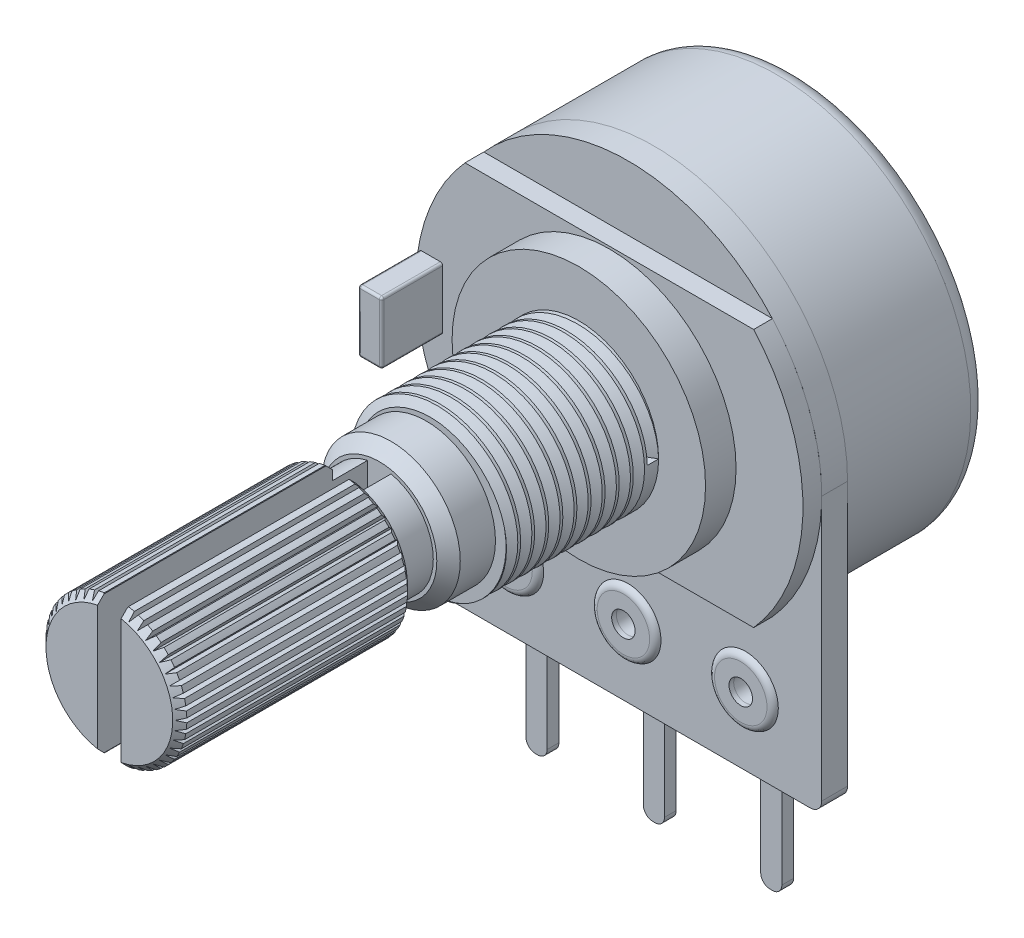
SolidWorks part; units mm, degrees
ref_plane "Ebene vorne" through (0, 0, 0) normal (0, 0, 1) x (1, 0, 0)
ref_plane "Ebene oben" through (0, 0, 0) normal (0, 1, 0) x (1, 0, 0)
ref_plane "Ebene rechts" through (0, 0, 0) normal (1, 0, 0) x (0, 0, -1)
sketch "Skizze1" plane through (0, 0, 0) normal (0, 0, 1) x (1, 0, 0)
  circle A0 centre (0, 0) radius 8.25
extrude "Aufsatz-Linear austragen1" add sketch "Skizze1" along normal blind 6
sketch "Skizze2" plane through (0, 0, 0) normal (0, 0, -1) x (-1, 0, 0)
  line L0 (8.25, 0) -> (6.85, 0)
  line L1 (6.85, 0) -> (6.85, -1.9)
  line L2 (6.85, -1.9) -> (8.0282, -1.9)
  circle A0 centre (0, 0) radius 8.25 construction
  arc A1 (8.25, 0) -> (8.0282, -1.9) centre (0, 0) cw
  dimension "D1" = 1.9
  dimension "D2" = 1.4
extrude "Schnitt-Linear austragen1" cut sketch "Skizze2" against normal blind 2.7
sketch "Skizze3" plane through (0, 0, 6) normal (0, 0, 1) x (1, 0, 0)
  line L0 (-8.25, 0) -> (-8.25, -11.75)
  line L1 (-8.25, -11.75) -> (8.25, -11.75)
  line L2 (8.25, -11.75) -> (8.25, 0)
  line L3 (0, 8.25) -> (19.4133, 8.25) construction
  line L4 (0, 0) -> (0, -11.75) construction
  arc A0 (8.25, 0) -> (-8.25, 0) centre (0, 0) ccw
  circle A1 centre (-5, -8.75) radius 0.5
  circle A2 centre (0, -8.75) radius 0.5
  circle A3 centre (5, -8.75) radius 0.5
  circle A4 centre (0, 0) radius 8.25 construction
  point P1 (0, 0)
  point P15 (0, 0)
  point P17 (0, 0)
  dimension "D2" = 1
  dimension "D1" = 20
  dimension "D3" = 3
  dimension "D4" = 10
extrude "Aufsatz-Linear austragen3" add sketch "Skizze3" along normal blind 1.1 separate body
sketch "Skizze4" plane through (0, 0, 6) normal (0, 0, -1) x (-1, 0, 0)
  line L0 (-6.8, -8.75) -> (-6.8, -12.75)
  line L1 (-6.8, -12.75) -> (-5.45, -12.75)
  line L2 (-5.45, -12.75) -> (-5.45, -16.3)
  line L3 (-5.05, -16.7) -> (-4.95, -16.7)
  line L4 (-4.55, -16.3) -> (-4.55, -12.75)
  line L5 (-4.55, -12.75) -> (-3.2, -12.75)
  line L6 (-3.2, -12.75) -> (-3.2, -8.75)
  line L7 (-5, -8.75) -> (-5, -16.7) construction
  line L8 (-5, -6.95) -> (-10.2754, -6.95) construction
  line L9 (-1.8, -8.75) -> (-1.8, -12.75)
  line L10 (-1.8, -12.75) -> (-0.45, -12.75)
  line L11 (-0.45, -12.75) -> (-0.45, -16.3)
  line L12 (-0.05, -16.7) -> (0.05, -16.7)
  line L13 (0.45, -16.3) -> (0.45, -12.75)
  line L14 (0.45, -12.75) -> (1.8, -12.75)
  line L15 (1.8, -12.75) -> (1.8, -8.75)
  line L16 (0, -8.75) -> (0, -16.7) construction
  line L17 (3.2, -8.75) -> (3.2, -12.75)
  line L18 (3.2, -12.75) -> (4.55, -12.75)
  line L19 (4.55, -12.75) -> (4.55, -16.3)
  line L20 (4.95, -16.7) -> (5.05, -16.7)
  line L21 (5.45, -16.3) -> (5.45, -12.75)
  line L22 (5.45, -12.75) -> (6.8, -12.75)
  line L23 (6.8, -12.75) -> (6.8, -8.75)
  line L24 (5, -8.75) -> (5, -16.7) construction
  arc A0 (-3.2, -8.75) -> (-6.8, -8.75) centre (-5, -8.75) ccw
  arc A1 (-4.95, -16.7) -> (-4.55, -16.3) centre (-4.95, -16.3) ccw
  arc A2 (-5.45, -16.3) -> (-5.05, -16.7) centre (-5.05, -16.3) ccw
  arc A3 (1.8, -8.75) -> (-1.8, -8.75) centre (0, -8.75) ccw
  arc A4 (0.05, -16.7) -> (0.45, -16.3) centre (0.05, -16.3) ccw
  arc A5 (-0.45, -16.3) -> (-0.05, -16.7) centre (-0.05, -16.3) ccw
  arc A6 (6.8, -8.75) -> (3.2, -8.75) centre (5, -8.75) ccw
  arc A7 (5.05, -16.7) -> (5.45, -16.3) centre (5.05, -16.3) ccw
  arc A8 (4.55, -16.3) -> (4.95, -16.7) centre (4.95, -16.3) ccw
  circle A9 centre (-5, -8.75) radius 0.5
  circle A10 centre (0, -8.75) radius 0.5
  circle A11 centre (5, -8.75) radius 0.5
  point P15 (-4.55, -16.7)
  point P18 (-5.45, -16.7)
  dimension "D1" = 0.9
  dimension "D5" = 0.4
  dimension "D2" = 3.6
  dimension "D3" = 5.8
  dimension "D4" = 9.75
  dimension "D6" = 3
extrude "Aufsatz-Linear austragen4" add sketch "Skizze4" along normal blind 0.5 separate body
sketch "Skizze5" plane through (0, 0, 7.1) normal (0, 0, 1) x (1, 0, 0)
  circle A0 centre (-5, -8.75) radius 1.4
  circle A1 centre (0, -8.75) radius 1.4
  circle A2 centre (5, -8.75) radius 1.4
  circle A3 centre (-5, -8.75) radius 0.5068
  circle A4 centre (0, -8.75) radius 0.5
  circle A5 centre (5, -8.75) radius 0.5
  dimension "D1" = 2.8
extrude "Aufsatz-Linear austragen5" add sketch "Skizze5" along normal blind 0.2 separate body
sketch "Skizze6" plane through (0, 0, 7.1) normal (0, 0, 1) x (1, 0, 0)
  line L0 (0, 0) -> (-5.8286, 0) construction
  line L1 (-6.1492, 5.5) -> (6.1492, 5.5)
  line L3 (-6.1492, -5.5) -> (6.1492, -5.5)
  arc A0 (6.1492, -5.5) -> (6.1492, 5.5) centre (0, 0) ccw
  arc A1 (-6.1492, 5.5) -> (-6.1492, -5.5) centre (0, 0) ccw
  dimension "D2" = 8.25
  dimension "D1" = 11
extrude "Aufsatz-Linear austragen6" add sketch "Skizze6" along normal blind 0.8 separate body
sketch "Skizze7" plane through (0, 0, 7.9) normal (0, 0, 1) x (1, 0, 0)
  line L1 (-8.1, 1.325) -> (-7.1, 1.325)
  line L2 (-8.1, 1.325) -> (-8.1, -1.325)
  line L3 (-8.1, -1.325) -> (-7.1, -1.325)
  line L4 (-7.1, 1.325) -> (-7.1, -1.325)
  line L5 (-8.1, 1.325) -> (-7.1, -1.325) construction
  line L6 (-8.1, -1.325) -> (-7.1, 1.325) construction
  circle A0 centre (0, 0) radius 5.4
  point P3 (-7.6, 0)
  point P8 (0, 0)
  dimension "D1" = 10.8
  dimension "D2" = 1
  dimension "D3" = 2.65
  dimension "D4" = 7.6
extrude "Aufsatz-Linear austragen7" add sketch "Skizze7" along normal blind 1.3 separate body contours A0 region at (0, 0, 7.9)
extrude "Aufsatz-Linear austragen8" add sketch "Skizze7<4>" along normal blind 2.6 contours L4 L1 L2 L3 region at (-7.6, 0, 7.9)
sketch "Skizze7<4>" plane through (0, 0, 7.9) normal (0, 0, 1) x (1, 0, 0) same geometry as "Skizze7"
fillet "Verrundung1" radius 0.1 8 edges at (-7.1, 0, 10.5) (-8.1, 0, 10.5) (-7.6, -1.325, 10.5) (-7.6, 1.325, 10.5) (-7.1, -1.325, 9.2) (-7.1, 1.325, 9.2) (-8.1, -1.325, 9.2) (-8.1, 1.325, 9.2)
sketch "Skizze8" plane through (0, 0, 9.2) normal (0, 0, 1) x (1, 0, 0)
  circle A0 centre (0, 0) radius 3.4
  dimension "D1" = 6.8
extrude "Aufsatz-Linear austragen9" add sketch "Skizze8" along normal blind 6.5
sketch "Skizze9" plane through (0, 0, 15.7) normal (0, 0, 1) x (1, 0, 0)
  circle A0 centre (0, 0) radius 2.95
  dimension "D1" = 5.9
extrude "Aufsatz-Linear austragen10" add sketch "Skizze9" along normal blind 2 contours A0
chamfer "Fase1" distance 0.5 angle 45 1 edges at (2.95, 0, 17.7)
sketch "Skizze10" plane through (0, 0, 17.7) normal (0, 0, 1) x (1, 0, 0)
  circle A0 centre (0, 0) radius 2.3
  dimension "D1" = 4.6
extrude "Aufsatz-Linear austragen11" add sketch "Skizze10" along normal blind 1.5
sketch "Skizze11" plane through (0, 0, 19.2) normal (0, 0, 1) x (1, 0, 0)
  circle A0 centre (0, 0) radius 3
  dimension "D1" = 6
extrude "Aufsatz-Linear austragen12" add sketch "Skizze11" along normal blind 10 contours A0
sketch "Skizze12" plane through (0, 0, 29.2) normal (0, 0, 1) x (1, 0, 0)
  line L1 (-0.5, 4) -> (0.5, 4)
  line L2 (-0.5, 4) -> (-0.5, -4)
  line L3 (-0.5, -4) -> (0.5, -4)
  line L4 (0.5, 4) -> (0.5, -4)
  line L5 (-0.5, 4) -> (0.5, -4) construction
  line L6 (-0.5, -4) -> (0.5, 4) construction
  point P0 (0, 0)
  dimension "D1" = 8
  dimension "D2" = 1
extrude "Schnitt-Linear austragen2" cut sketch "Skizze12" against normal blind 11.5
thread "Gewinde1" pitch 0.5 method cut trim with end face yes profile "Gewindeprofil1" start angle 0, offset 0, length 6.5, pitch 0.6, diameter 6.8
ref_plane "Ebene1" through (3.4, 0, 9.2) normal (0, 1, 0) x (-1, 0, 0)
sketch "Gewindeprofil1" plane through (3.4, 0, 9.2) normal (0, 1, 0) x (-1, 0, 0)
  line L0 (0, 0) -> (0, 0.5) construction
  line L1 (0, 0) -> (0.4, 0.2309)
  line L2 (0.4, 0.2309) -> (0.4, 0.2509)
  line L3 (0.4, 0.2509) -> (0, 0.4819)
  line L4 (0.4, 0.2409) -> (0, 0.2409) construction
  line L11 (0, 0) -> (0, 0.4819)
  point P2 (0, 0)
  dimension "Pitch" = 0.5
  dimension "Profile_Angle" = 60
  dimension "Profile_Land" = 0.02
  dimension "Profile_Height" = 0.4
chamfer "Fase2" distance 0.3 angle 45 4 edges at (3, 0, 19.2) (-3, 0, 19.2) (3, 0, 29.2) (-3, 0, 29.2)
sketch "Skizze18" plane through (0, 0, 29.2) normal (0, 0, 1) x (1, 0, 0)
  line L0 (0, 0) -> (-3.0768, 0) construction
  line L1 (-3.3157, -0.2) -> (-2.75, 0)
  line L2 (-2.75, 0) -> (-3.3157, 0.2)
  line L3 (-3.3157, 0.2) -> (-3.3157, -0.2)
  line L4 (-3.3104, 0.2739) -> (-2.722, 0.3914)
  line L5 (-2.722, 0.3914) -> (-3.2535, 0.6698)
  line L6 (-3.2535, 0.6698) -> (-3.3104, 0.2739)
  line L7 (-3.2377, 0.7422) -> (-2.6386, 0.7748)
  line L8 (-2.6386, 0.7748) -> (-3.125, 1.126)
  line L9 (-3.125, 1.126) -> (-3.2377, 0.7422)
  line L10 (-3.0991, 1.1955) -> (-2.5015, 1.1424)
  line L11 (-2.5015, 1.1424) -> (-2.933, 1.5593)
  line L12 (-2.933, 1.5593) -> (-3.0991, 1.1955)
  line L13 (-2.8975, 1.6243) -> (-2.3134, 1.4868)
  line L14 (-2.3134, 1.4868) -> (-2.6812, 1.9608)
  line L15 (-2.6812, 1.9608) -> (-2.8975, 1.6243)
  line L16 (-2.6368, 2.0202) -> (-2.0783, 1.8009)
  line L17 (-2.0783, 1.8009) -> (-2.3749, 2.3225)
  line L18 (-2.3749, 2.3225) -> (-2.6368, 2.0202)
  line L19 (-2.3225, 2.3749) -> (-1.8009, 2.0783)
  line L20 (-1.8009, 2.0783) -> (-2.0202, 2.6368)
  line L21 (-2.0202, 2.6368) -> (-2.3225, 2.3749)
  line L22 (-1.9608, 2.6812) -> (-1.4868, 2.3134)
  line L23 (-1.4868, 2.3134) -> (-1.6243, 2.8975)
  line L24 (-1.6243, 2.8975) -> (-1.9608, 2.6812)
  line L25 (-1.5593, 2.933) -> (-1.1424, 2.5015)
  line L26 (-1.1424, 2.5015) -> (-1.1955, 3.0991)
  line L27 (-1.1955, 3.0991) -> (-1.5593, 2.933)
  line L28 (-1.126, 3.125) -> (-0.7748, 2.6386)
  line L29 (-0.7748, 2.6386) -> (-0.7422, 3.2377)
  line L30 (-0.7422, 3.2377) -> (-1.126, 3.125)
  line L31 (-0.6698, 3.2535) -> (-0.3914, 2.722)
  line L32 (-0.3914, 2.722) -> (-0.2739, 3.3104)
  line L33 (-0.2739, 3.3104) -> (-0.6698, 3.2535)
  line L34 (-0.2, 3.3157) -> (0, 2.75)
  line L35 (0, 2.75) -> (0.2, 3.3157)
  line L36 (0.2, 3.3157) -> (-0.2, 3.3157)
  line L37 (0.2739, 3.3104) -> (0.3914, 2.722)
  line L38 (0.3914, 2.722) -> (0.6698, 3.2535)
  line L39 (0.6698, 3.2535) -> (0.2739, 3.3104)
  line L40 (0.7422, 3.2377) -> (0.7748, 2.6386)
  line L41 (0.7748, 2.6386) -> (1.126, 3.125)
  line L42 (1.126, 3.125) -> (0.7422, 3.2377)
  line L43 (1.1955, 3.0991) -> (1.1424, 2.5015)
  line L44 (1.1424, 2.5015) -> (1.5593, 2.933)
  line L45 (1.5593, 2.933) -> (1.1955, 3.0991)
  line L46 (1.6243, 2.8975) -> (1.4868, 2.3134)
  line L47 (1.4868, 2.3134) -> (1.9608, 2.6812)
  line L48 (1.9608, 2.6812) -> (1.6243, 2.8975)
  line L49 (2.0202, 2.6368) -> (1.8009, 2.0783)
  line L50 (1.8009, 2.0783) -> (2.3225, 2.3749)
  line L51 (2.3225, 2.3749) -> (2.0202, 2.6368)
  line L52 (2.3749, 2.3225) -> (2.0783, 1.8009)
  line L53 (2.0783, 1.8009) -> (2.6368, 2.0202)
  line L54 (2.6368, 2.0202) -> (2.3749, 2.3225)
  line L55 (2.6812, 1.9608) -> (2.3134, 1.4868)
  line L56 (2.3134, 1.4868) -> (2.8975, 1.6243)
  line L57 (2.8975, 1.6243) -> (2.6812, 1.9608)
  line L58 (2.933, 1.5593) -> (2.5015, 1.1424)
  line L59 (2.5015, 1.1424) -> (3.0991, 1.1955)
  line L60 (3.0991, 1.1955) -> (2.933, 1.5593)
  line L61 (3.125, 1.126) -> (2.6386, 0.7748)
  line L62 (2.6386, 0.7748) -> (3.2377, 0.7422)
  line L63 (3.2377, 0.7422) -> (3.125, 1.126)
  line L64 (3.2535, 0.6698) -> (2.722, 0.3914)
  line L65 (2.722, 0.3914) -> (3.3104, 0.2739)
  line L66 (3.3104, 0.2739) -> (3.2535, 0.6698)
  line L67 (3.3157, 0.2) -> (2.75, 0)
  line L68 (2.75, 0) -> (3.3157, -0.2)
  line L69 (3.3157, -0.2) -> (3.3157, 0.2)
  line L70 (3.3104, -0.2739) -> (2.722, -0.3914)
  line L71 (2.722, -0.3914) -> (3.2535, -0.6698)
  line L72 (3.2535, -0.6698) -> (3.3104, -0.2739)
  line L73 (3.2377, -0.7422) -> (2.6386, -0.7748)
  line L74 (2.6386, -0.7748) -> (3.125, -1.126)
  line L75 (3.125, -1.126) -> (3.2377, -0.7422)
  line L76 (3.0991, -1.1955) -> (2.5015, -1.1424)
  line L77 (2.5015, -1.1424) -> (2.933, -1.5593)
  line L78 (2.933, -1.5593) -> (3.0991, -1.1955)
  line L79 (2.8975, -1.6243) -> (2.3134, -1.4868)
  line L80 (2.3134, -1.4868) -> (2.6812, -1.9608)
  line L81 (2.6812, -1.9608) -> (2.8975, -1.6243)
  line L82 (2.6368, -2.0202) -> (2.0783, -1.8009)
  line L83 (2.0783, -1.8009) -> (2.3749, -2.3225)
  line L84 (2.3749, -2.3225) -> (2.6368, -2.0202)
  line L85 (2.3225, -2.3749) -> (1.8009, -2.0783)
  line L86 (1.8009, -2.0783) -> (2.0202, -2.6368)
  line L87 (2.0202, -2.6368) -> (2.3225, -2.3749)
  line L88 (1.9608, -2.6812) -> (1.4868, -2.3134)
  line L89 (1.4868, -2.3134) -> (1.6243, -2.8975)
  line L90 (1.6243, -2.8975) -> (1.9608, -2.6812)
  line L91 (1.5593, -2.933) -> (1.1424, -2.5015)
  line L92 (1.1424, -2.5015) -> (1.1955, -3.0991)
  line L93 (1.1955, -3.0991) -> (1.5593, -2.933)
  line L94 (1.126, -3.125) -> (0.7748, -2.6386)
  line L95 (0.7748, -2.6386) -> (0.7422, -3.2377)
  line L96 (0.7422, -3.2377) -> (1.126, -3.125)
  line L97 (0.6698, -3.2535) -> (0.3914, -2.722)
  line L98 (0.3914, -2.722) -> (0.2739, -3.3104)
  line L99 (0.2739, -3.3104) -> (0.6698, -3.2535)
  line L100 (0.2, -3.3157) -> (0, -2.75)
  line L101 (0, -2.75) -> (-0.2, -3.3157)
  line L102 (-0.2, -3.3157) -> (0.2, -3.3157)
  line L103 (-0.2739, -3.3104) -> (-0.3914, -2.722)
  line L104 (-0.3914, -2.722) -> (-0.6698, -3.2535)
  line L105 (-0.6698, -3.2535) -> (-0.2739, -3.3104)
  line L106 (-0.7422, -3.2377) -> (-0.7748, -2.6386)
  line L107 (-0.7748, -2.6386) -> (-1.126, -3.125)
  line L108 (-1.126, -3.125) -> (-0.7422, -3.2377)
  line L109 (-1.1955, -3.0991) -> (-1.1424, -2.5015)
  line L110 (-1.1424, -2.5015) -> (-1.5593, -2.933)
  line L111 (-1.5593, -2.933) -> (-1.1955, -3.0991)
  line L112 (-1.6243, -2.8975) -> (-1.4868, -2.3134)
  line L113 (-1.4868, -2.3134) -> (-1.9608, -2.6812)
  line L114 (-1.9608, -2.6812) -> (-1.6243, -2.8975)
  line L115 (-2.0202, -2.6368) -> (-1.8009, -2.0783)
  line L116 (-1.8009, -2.0783) -> (-2.3225, -2.3749)
  line L117 (-2.3225, -2.3749) -> (-2.0202, -2.6368)
  line L118 (-2.3749, -2.3225) -> (-2.0783, -1.8009)
  line L119 (-2.0783, -1.8009) -> (-2.6368, -2.0202)
  line L120 (-2.6368, -2.0202) -> (-2.3749, -2.3225)
  line L121 (-2.6812, -1.9608) -> (-2.3134, -1.4868)
  line L122 (-2.3134, -1.4868) -> (-2.8975, -1.6243)
  line L123 (-2.8975, -1.6243) -> (-2.6812, -1.9608)
  line L124 (-2.933, -1.5593) -> (-2.5015, -1.1424)
  line L125 (-2.5015, -1.1424) -> (-3.0991, -1.1955)
  line L126 (-3.0991, -1.1955) -> (-2.933, -1.5593)
  line L127 (-3.125, -1.126) -> (-2.6386, -0.7748)
  line L128 (-2.6386, -0.7748) -> (-3.2377, -0.7422)
  line L129 (-3.2377, -0.7422) -> (-3.125, -1.126)
  line L130 (-3.2535, -0.6698) -> (-2.722, -0.3914)
  line L131 (-2.722, -0.3914) -> (-3.3104, -0.2739)
  line L132 (-3.3104, -0.2739) -> (-3.2535, -0.6698)
  point P138 (0, 0)
  dimension "D1" = 0.6
  dimension "D2" = 0.4
  dimension "D3" = 2.75
  dimension "D4" = 44
extrude "Schnitt-Linear austragen3" cut sketch "Skizze18" against normal blind 10
fillet "Verrundung2" radius 0.75 1 edges at (8.1944, 0.9564, 0)
fillet "Verrundung3" radius 0.5 2 edges at (8.25, -11.75, 6.55) (-8.25, -11.75, 6.55)
fillet "Verrundung4" radius 0.3 1 edges at (-3.6, -8.75, 7.3)
fillet "Verrundung5" radius 0.3 1 edges at (1.4, -8.75, 7.3)
fillet "Verrundung6" radius 0.3 1 edges at (6.4, -8.75, 7.3)
